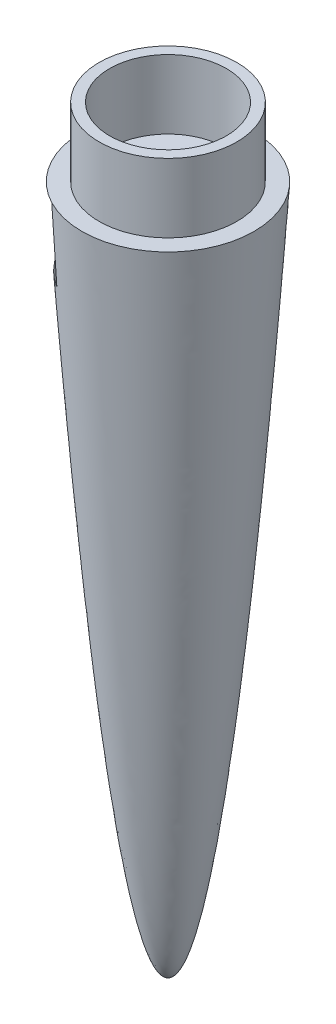
SolidWorks part; units mm, degrees
ref_plane "Front Plane" through (0, 0, 0) normal (0, 0, 1) x (1, 0, 0)
ref_plane "Top Plane" through (0, 0, 0) normal (0, 1, 0) x (1, 0, 0)
ref_plane "Right Plane" through (0, 0, 0) normal (1, 0, 0) x (0, 0, -1)
sketch "Sketch4" plane through (0, 0, 0) normal (1, 0, 0) x (0, 0, -1)
  line L2 (0, -0.0389) -> (0, 76.2113) construction
  line L4 (-7.9376, 63.4611) -> (-6.35, 63.4611)
  line L7 (-6.35, 63.4611) -> (-6.35, 69.8111)
  line L8 (-6.35, 69.8111) -> (-5.3823, 69.8111)
  line L9 (-5.3823, 63.4611) -> (-5.3823, 69.8111)
  line L10 (-5.3823, 63.4611) -> (0, 63.4611)
  line L11 (0, 2.142) -> (0, 0)
  line L12 (-6.6184, 62.1097) -> (0, 62.1097)
  line L13 (0, 63.4611) -> (0, 62.1097)
  spline S0 degree 4 poles (0, 2.142) (-0.0301, 2.142) (-0.071, 2.1467) (-0.1222, 2.1612) (-0.1848, 2.191) (-0.2329, 2.2205) (-0.2873, 2.262) (-0.351, 2.3217) (-0.4275, 2.4085) (-0.5263, 2.5455) (-0.6621, 2.7768) (-0.8605, 3.2063) (-1.1667, 4.0723) (-1.6403, 5.9122) (-2.1747, 8.8173) (-2.7282, 12.6928) (-3.2633, 17.2492) (-3.744, 21.9769) (-4.172, 26.6662) (-4.5678, 31.4271) (-4.9289, 36.0792) (-5.2779, 40.9148) (-5.591, 45.4531) (-5.9167, 50.4842) (-6.182, 54.7032) (-6.4827, 59.7561) (-6.6506, 62.6539) (-6.7993, 65.2821) (-6.9083, 67.2216) (-6.9259, 67.556) (-6.9604, 68.1693) knots 0 0 0 0 0 0.001792 0.002467 0.003169 0.004143 0.005173 0.006564 0.008395 0.011072 0.015284 0.022639 0.036701 0.066151 0.128986 0.19998 0.270974 0.341968 0.412962 0.483956 0.554951 0.625945 0.696939 0.767933 0.838927 0.909921 0.954961 0.97748 1 1 1 1 1 construction
  spline S1 degree 4 poles (0, 2.142) (-0.0301, 2.142) (-0.071, 2.1467) (-0.1222, 2.1612) (-0.1848, 2.191) (-0.2329, 2.2205) (-0.2873, 2.262) (-0.351, 2.3217) (-0.4275, 2.4085) (-0.5263, 2.5455) (-0.6621, 2.7768) (-0.8605, 3.2063) (-1.1667, 4.0723) (-1.6403, 5.9122) (-2.1747, 8.8173) (-2.7282, 12.6928) (-3.2633, 17.2492) (-3.744, 21.9769) (-4.172, 26.6662) (-4.5678, 31.4271) (-4.9289, 36.0792) (-5.2779, 40.9148) (-5.591, 45.4531) (-5.9167, 50.4842) (-6.182, 54.7032) (-6.4302, 58.874) (-6.5564, 61.0343) (-6.6184, 62.1097) knots 0 0 0 0 0 0.001792 0.002467 0.003169 0.004143 0.005173 0.006564 0.008395 0.011072 0.015284 0.022639 0.036701 0.066151 0.128986 0.19998 0.270974 0.341968 0.412962 0.483956 0.554951 0.625945 0.696939 0.767933 0.838927 0.909921 0.909921 0.909921 0.909921 0.909921
  spline S2 degree 4 poles (0, 0) (-0.0369, -0.0001) (-0.0857, 0.0049) (-0.1472, 0.0201) (-0.2239, 0.0521) (-0.2835, 0.0844) (-0.3519, 0.1307) (-0.4322, 0.1981) (-0.5281, 0.2957) (-0.6496, 0.4473) (-0.8101, 0.6931) (-1.0368, 1.1292) (-1.3777, 1.9711) (-1.8936, 3.6858) (-2.5213, 6.549) (-3.1805, 10.4791) (-3.8279, 15.203) (-4.4238, 20.2846) (-4.952, 25.3273) (-5.438, 30.4468) (-5.8804, 35.453) (-6.3066, 40.6522) (-6.6888, 45.5403) (-7.0847, 50.9452) (-7.4083, 55.4998) (-7.7709, 60.8988) (-7.9755, 64.0296) (-8.152, 66.797) (-8.2847, 68.8901) (-8.3035, 69.2115) (-8.3458, 69.8785) knots 0 0 0 0 0 0.00207 0.002771 0.003558 0.00469 0.005895 0.007433 0.009472 0.012413 0.016849 0.024014 0.037179 0.063737 0.117806 0.189835 0.261865 0.333894 0.405923 0.477952 0.549982 0.622011 0.69404 0.766069 0.838098 0.910128 0.955064 0.977532 1 1 1 1 1 construction
  spline S3 degree 4 poles (0, 0) (-0.0369, -0.0001) (-0.0857, 0.0049) (-0.1472, 0.0201) (-0.2239, 0.0521) (-0.2835, 0.0844) (-0.3519, 0.1307) (-0.4322, 0.1981) (-0.5281, 0.2957) (-0.6496, 0.4473) (-0.8101, 0.6931) (-1.0368, 1.1292) (-1.3777, 1.9711) (-1.8936, 3.6858) (-2.5213, 6.549) (-3.1805, 10.4791) (-3.8279, 15.203) (-4.4238, 20.2846) (-4.952, 25.3273) (-5.438, 30.4468) (-5.8804, 35.453) (-6.3066, 40.6522) (-6.6888, 45.5403) (-7.0847, 50.9452) (-7.4083, 55.4998) (-7.7085, 59.9694) (-7.8623, 62.3036) (-7.9376, 63.4611) knots 0 0 0 0 0 0.00207 0.002771 0.003558 0.00469 0.005895 0.007433 0.009472 0.012413 0.016849 0.024014 0.037179 0.063737 0.117806 0.189835 0.261865 0.333894 0.405923 0.477952 0.549982 0.622011 0.69404 0.766069 0.838098 0.910128 0.910128 0.910128 0.910128 0.910128
  dimension "D1" = 0.9677
  dimension "D2" = 7.9376
  dimension "D3" = 63.5
  dimension "D4" = 6.35
revolve "Revolve2" add sketch "Sketch4" angle 360 about L2
